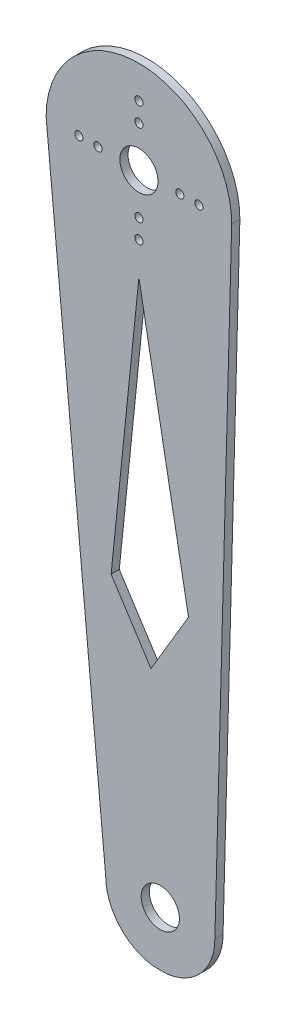
SolidWorks part; units mm, degrees
ref_plane "前视基准面" through (0, 0, 0) normal (0, 0, 1) x (1, 0, 0)
ref_plane "上视基准面" through (0, 0, 0) normal (0, 1, 0) x (1, 0, 0)
ref_plane "右视基准面" through (0, 0, 0) normal (1, 0, 0) x (0, 0, -1)
sketch "草图1" plane through (0, 0, 0) normal (0, 0, 1) x (1, 0, 0)
  line L0 (34, 0) -> (42.4817, -249.8561)
  line L1 (-34, 0) -> (-25.5183, -249.8561)
  line L2 (-25.5183, -249.8561) -> (42.4817, -249.8561)
  arc A0 (-34, 0) -> (34, 0) centre (0, 0) cw
extrude "凸台-拉伸1" add sketch "草图1" along normal blind 3
sketch "草图2" plane through (0, 0, 0) normal (0, 0, -1) x (-1, 0, 0)
  arc A0 (34, 0) -> (-34, 0) centre (0, 0) cw
sketch "草图3" plane through (0, 0, 3) normal (0, 0, 1) x (1, 0, 0)
  line L0 (-34, 0) -> (-25.5183, -249.8561) construction
  line L2 (-34, 0) -> (-12.1722, -230.0172)
  line L3 (34, 0) -> (27.8278, -230.0172)
  circle A0 centre (7.8278, -230.0172) radius 20
  line M2 (-34, 0) -> (-25.5183, -249.8561)
  line M3 (-25.5183, -249.8561) -> (42.4817, -249.8561)
  line M4 (42.4817, -249.8561) -> (34, 0)
  dimension "D1" = 34
extrude "切除-拉伸1" cut sketch "草图3" against normal blind 3 contours A0 L2 M2 M3 region at (-22.7317, -169.1648, 3)
sketch "草图4" plane through (0, 0, 3) normal (0, 0, 1) x (1, 0, 0)
extrude "切除-拉伸2" cut sketch "草图3<4>" against normal blind 3 contours A0 L3 M3 M4 region at (34.1465, -169.6743, 3)
sketch "草图3<4>" plane through (0, 0, 3) normal (0, 0, 1) x (1, 0, 0) same geometry as "草图3"
sketch "草图5" plane through (0, 0, 3) normal (0, 0, 1) x (1, 0, 0)
  circle A2 centre (0, 22) radius 1.5
  circle A3 centre (0, 15) radius 1.5
  circle A4 centre (-22, 0) radius 1.5
  circle A5 centre (-15, 0) radius 1.5
  circle A6 centre (0, -15) radius 1.5
  circle A7 centre (15, 0) radius 1.5
  circle A8 centre (22, 0) radius 1.5
  circle A9 centre (0, -22) radius 1.5
extrude "切除-拉伸3" cut sketch "草图5" against normal blind 3
sketch "草图6" plane through (0, 0, 3) normal (0, 0, 1) x (1, 0, 0)
  line L7 (0, -34) -> (-10.1835, -133.2316)
  line L8 (-10.1835, -133.2316) -> (4.422, -155.9402)
  line L9 (4.422, -155.9402) -> (18.167, -132.7006)
  line L10 (18.167, -132.7006) -> (0, -34)
  arc A0 (-34, 0) -> (34, 0) centre (0, 0) ccw construction
extrude "切除-拉伸4" cut sketch "草图6" against normal blind 3 contours L7 L8 L9 L10
sketch "草图7" plane through (0, 0, 3) normal (0, 0, 1) x (1, 0, 0)
  circle A0 centre (7.8278, -230.0172) radius 7
extrude "切除-拉伸5" cut sketch "草图7" against normal blind 3
sketch "草图8" plane through (0, 0, 3) normal (0, 0, 1) x (1, 0, 0)
  circle A0 centre (0, 0) radius 7
extrude "切除-拉伸6" cut sketch "草图8" against normal blind 10
